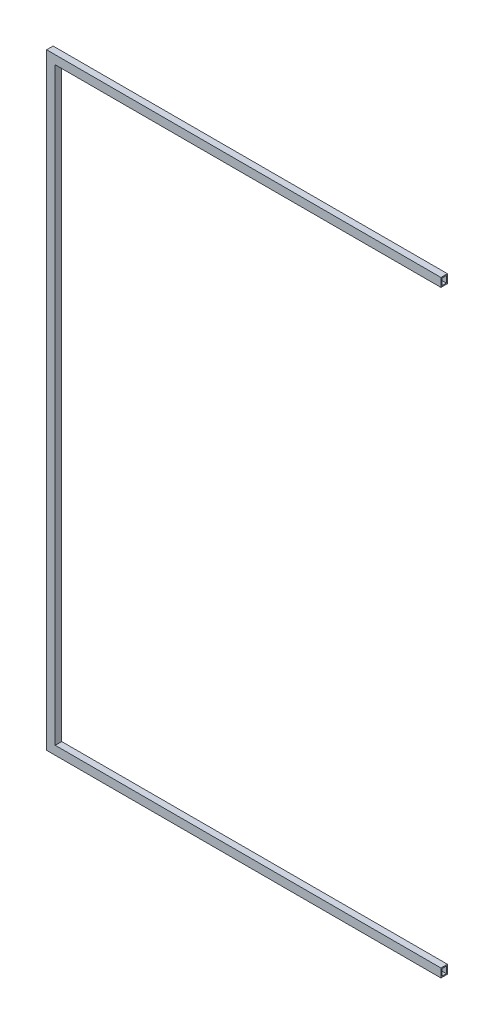
SolidWorks part; units mm, degrees
material "PC High Viscosity"
ref_plane "Front Plane" through (0, 0, 0) normal (0, 0, 1) x (1, 0, 0)
ref_plane "Top Plane" through (0, 0, 0) normal (0, 1, 0) x (1, 0, 0)
ref_plane "Right Plane" through (0, 0, 0) normal (1, 0, 0) x (0, 0, -1)
sketch "Sketch1" plane through (0, 0, 0) normal (0, 0, 1) x (1, 0, 0)
  line L1 (0, 0) -> (577.85, 0)
  line L2 (0, 0) -> (0, 863.6)
  line L3 (0, 863.6) -> (577.85, 863.6)
  line L4 (577.85, 0) -> (577.85, 863.6)
  dimension "D1" = 863.6
  dimension "D2" = 577.85
sketch "Sketch2" plane through (0, 0, 0) normal (0, 0, 1) x (1, 0, 0)
  line L0 (0, 0) -> (0, 863.6) construction
  line L1 (3.175, -12.7) -> (581.025, -12.7)
  line L2 (3.175, -12.7) -> (3.175, 876.3)
  line L3 (3.175, 876.3) -> (581.025, 876.3)
  line L4 (581.025, -12.7) -> (581.025, 876.3)
  line L5 (577.85, 0) -> (577.85, 863.6) construction
  line L6 (0, 863.6) -> (577.85, 863.6) construction
  line L7 (0, 0) -> (577.85, 0) construction
  dimension "D1" = 3.175
  dimension "D2" = 3.175
  dimension "D3" = 12.7
  dimension "D4" = 12.7
extrude "Boss-Extrude1" add sketch "Sketch2" along normal mid plane 9.525
sketch "Sketch3" plane through (0, 0, 4.7625) normal (0, 0, 1) x (1, 0, 0)
  line L1 (581.025, -12.7) -> (581.025, 876.3) construction
  line L8 (15.875, 863.6) -> (15.875, 0)
  line L9 (15.875, 0) -> (568.325, 0)
  line L10 (568.325, 0) -> (568.325, 863.6)
  line L11 (568.325, 863.6) -> (15.875, 863.6)
  line L12 (15.875, 863.6) -> (15.875, 0)
  line L13 (15.875, 0) -> (581.025, 0)
  line L14 (581.025, 0) -> (581.025, 863.6)
  line L15 (581.025, 863.6) -> (15.875, 863.6)
  point P0 (789.6888, 0)
  point P2 (568.325, 863.6)
  point P4 (568.325, 0)
  dimension "D1" = 12.7
extrude "Cut-Extrude1" cut sketch "Sketch3" against normal through all
sketch "Sketch4" plane through (0, 0, 0) normal (0, 0, 1) x (1, 0, 0)
  line L0 (581.025, 863.6) -> (581.025, 876.3) construction
  line L1 (581.025, -12.7) -> (581.025, 0) construction
  line L8 (4.7625, 874.7125) -> (4.7625, -11.1125)
  line L9 (4.7625, -11.1125) -> (579.4375, -11.1125)
  line L10 (579.4375, -11.1125) -> (579.4375, -1.5875)
  line L11 (579.4375, 874.7125) -> (4.7625, 874.7125)
  line L12 (4.7625, 874.7125) -> (4.7625, -11.1125)
  line L13 (4.7625, -11.1125) -> (581.025, -11.1125)
  line L14 (581.025, -11.1125) -> (581.025, -1.5875)
  line L15 (581.025, 874.7125) -> (4.7625, 874.7125)
  line L16 (14.2875, -1.5875) -> (14.2875, 865.1875)
  line L17 (14.2875, -1.5875) -> (14.2875, 865.1875)
  line L18 (14.2875, 865.1875) -> (579.4375, 865.1875)
  line L19 (14.2875, 865.1875) -> (581.025, 865.1875)
  line L20 (579.4375, 865.1875) -> (579.4375, 874.7125)
  line L21 (581.025, 865.1875) -> (581.025, 874.7125)
  line L22 (579.4375, -1.5875) -> (14.2875, -1.5875)
  line L23 (581.025, -1.5875) -> (14.2875, -1.5875)
  point P0 (585.5613, -11.1125)
  dimension "D1" = 1.5875
extrude "Cut-Extrude2" cut sketch "Sketch4" along normal offset from surface 1.5875 and the other way offset from surface 1.5875 up to face at (295.275, 431.8, 4.7625) other way up to face at (295.275, 431.8, -4.7625)
sketch "Sketch5" plane through (0, 0, 4.7625) normal (0, 0, 1) x (1, 0, 0)
  line L0 (581.025, 876.3) -> (568.325, 863.6)
  line L1 (581.025, -12.7) -> (568.325, 0)
  line L2 (3.175, -12.7) -> (15.875, 0)
  line L3 (3.175, 876.3) -> (15.875, 863.6)
  line L4 (581.025, 863.6) -> (15.875, 863.6) construction
  line L5 (15.875, 0) -> (581.025, 0) construction
  point P16 (0, 0)
  point P17 (568.325, 863.6)
  point P20 (0, 0)
  point P21 (0, 0)
